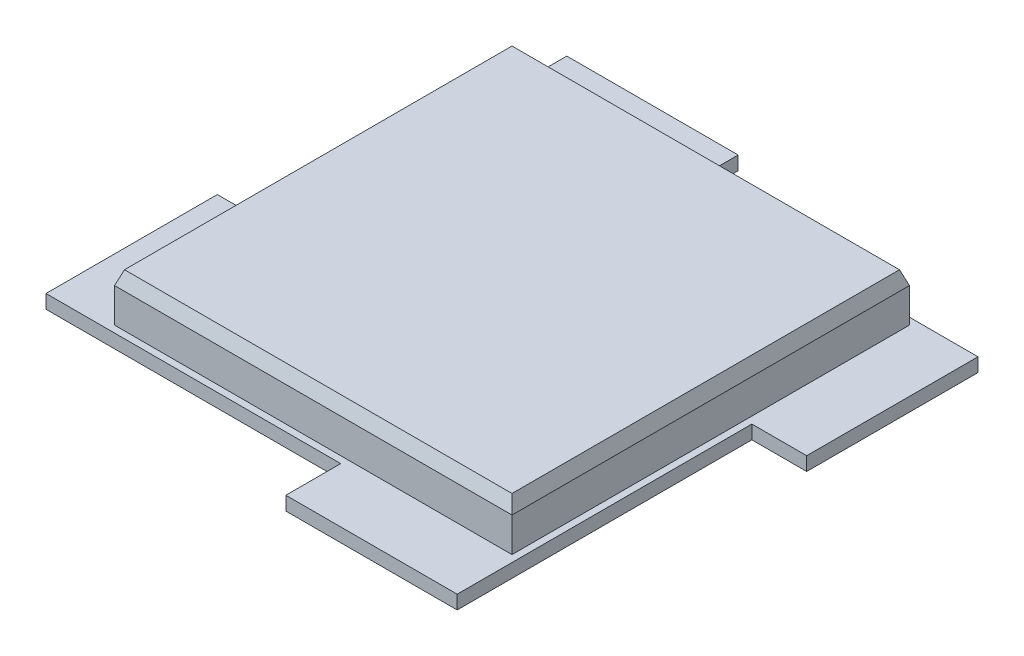
SolidWorks part; units mm, degrees
material "Acrylique (impact moyen-haut)"
ref_plane "Plan de face" through (0, 0, 0) normal (0, 0, 1) x (1, 0, 0)
ref_plane "Plan de dessus" through (0, 0, 0) normal (0, 1, 0) x (1, 0, 0)
ref_plane "Plan de droite" through (0, 0, 0) normal (1, 0, 0) x (0, 0, -1)
sketch "Esquisse1" plane through (0, 0, 0) normal (0, 1, 0) x (1, 0, 0)
  line L0 (0, 0) -> (8, 0) construction
  line L1 (8, 0) -> (8, 8) construction
  line L2 (8, 8) -> (68, 8)
  line L3 (68, 8) -> (68, 68)
  line L4 (68, 68) -> (8, 68)
  line L5 (8, 68) -> (8, 8)
  line L6 (8, 8) -> (0, 8)
  line L7 (0, 8) -> (0, 33)
  line L8 (8, 33) -> (0, 33)
  line L9 (68, 43) -> (76, 43)
  line L10 (76, 43) -> (76, 68)
  line L11 (76, 68) -> (68, 68)
  line L12 (33, 68) -> (33, 76)
  line L13 (33, 76) -> (8, 76)
  line L14 (8, 76) -> (8, 68)
  line L15 (43, 8) -> (43, 0)
  line L16 (43, 0) -> (68, 0)
  line L17 (68, 0) -> (68, 8)
  dimension "D1" = 60
  dimension "D2" = 60
  dimension "D3" = 8
  dimension "D4" = 8
  dimension "D5" = 25
  dimension "D6" = 8
  dimension "D7" = 8
  dimension "D8" = 8
  dimension "D9" = 8
  dimension "D10" = 8
  dimension "D11" = 25
  dimension "D12" = 25
  dimension "D13" = 25
extrude "Boss.-Extru.1" add sketch "Esquisse1" along normal blind 2 contours L5 L8 L7 L6 | L13 L14 L4 L12 | L10 L11 L3 L9 | L16 L17 L2 L15 | L4 L5 L2 L3 region at (38, 0, -38) region at (4, 0, -20.5) region at (55.5, 0, -4) region at (20.5, 0, -72) region at (72, 0, -55.5)
sketch "Esquisse2" plane through (0, 2, 0) normal (0, 1, 0) x (1, 0, 0)
  line L0 (76, 68) -> (33, 68) construction
  line L1 (68, 0) -> (68, 43) construction
  line L2 (67, 67) -> (67, 9)
  line L3 (67, 67) -> (9, 67)
  line L4 (9, 67) -> (9, 9)
  line L5 (9, 9) -> (67, 9)
  line L6 (43, 8) -> (0, 8) construction
  line L7 (8, 76) -> (8, 33) construction
  dimension "D1" = 1
  dimension "D2" = 1
  dimension "D3" = 1
  dimension "D4" = 1
extrude "Boss.-Extru.2" add sketch "Esquisse2" along normal blind 5
extrude "Boss.-Extru.3" add sketch "Esquisse2<3>" along normal blind 2 draft 20 from offset 5 contours L4 L5 L2 L3 region at (38, 2, -38)
sketch "Esquisse2<3>" plane through (0, 2, 0) normal (0, 1, 0) x (1, 0, 0) same geometry as "Esquisse2"
